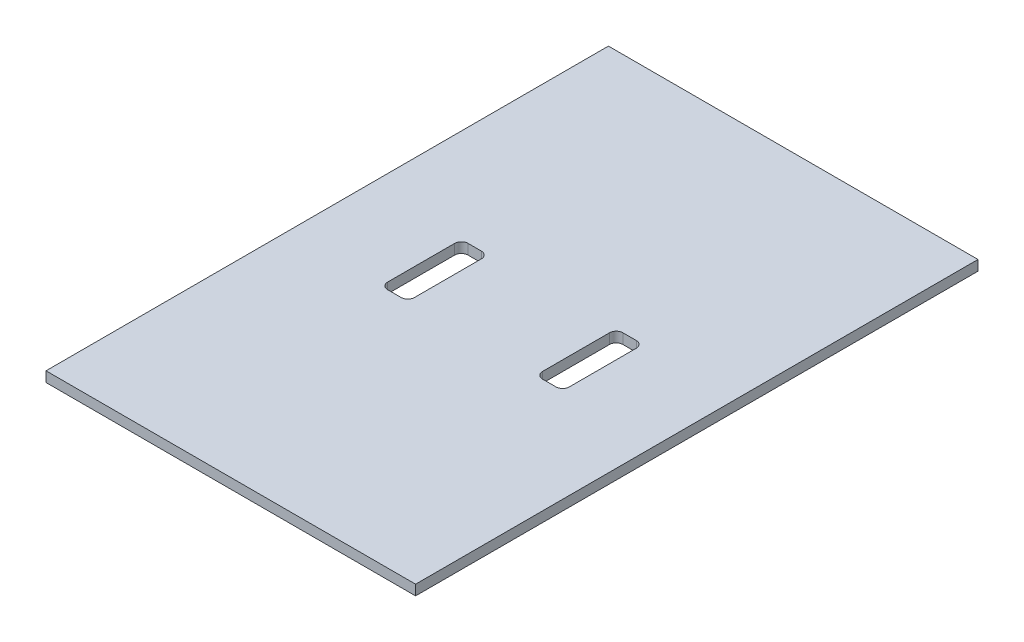
SolidWorks part; units mm, degrees
material "6061-T6 (SS)"
ref_plane "Front Plane" through (0, 0, 0) normal (0, 0, 1) x (1, 0, 0)
ref_plane "Top Plane" through (0, 0, 0) normal (0, 1, 0) x (1, 0, 0)
ref_plane "Right Plane" through (0, 0, 0) normal (1, 0, 0) x (0, 0, -1)
sketch "Sketch1" plane through (0, 0, 0) normal (0, 1, 0) x (1, 0, 0)
  line L1 (-87.63, 133.35) -> (87.63, 133.35)
  line L2 (-87.63, 133.35) -> (-87.63, -133.35)
  line L3 (-87.63, -133.35) -> (87.63, -133.35)
  line L4 (87.63, 133.35) -> (87.63, -133.35)
  line L5 (-87.63, 133.35) -> (87.63, -133.35) construction
  line L6 (-87.63, -133.35) -> (87.63, 133.35) construction
  point P0 (0, 0)
  dimension "D1" = 175.26
  dimension "D2" = 266.7
extrude "Boss-Extrude1" add sketch "Sketch1" along normal blind 4.826
sketch "Sketch2" plane through (0, 4.826, 0) normal (0, 1, 0) x (1, 0, 0)
  line L0 (-87.63, 133.35) -> (-87.63, -133.35) construction
  line L1 (-43.0665, 19.05) -> (-30.3665, 19.05)
  line L2 (-43.0665, 19.05) -> (-43.0665, -19.05)
  line L3 (-43.0665, -19.05) -> (-30.3665, -19.05)
  line L4 (-30.3665, 19.05) -> (-30.3665, -19.05)
  line L5 (-43.0665, 19.05) -> (-30.3665, -19.05) construction
  line L6 (-43.0665, -19.05) -> (-30.3665, 19.05) construction
  point P0 (-36.7165, 0)
  point P7 (0, 0)
  point P8 (0, 0)
  dimension "D1" = 50.9135
  dimension "D2" = 12.7
  dimension "D3" = 38.1
extrude "Cut-Extrude1" cut sketch "Sketch2" against normal through all
mirror "Mirror1" about plane through (0, 0, 0) normal (1, 0, 0) of "Cut-Extrude1"
fillet "Fillet1" radius 3.175 8 edges at (43.0665, 2.413, 19.05) (30.3665, 2.413, 19.05) (43.0665, 2.413, -19.05) (30.3665, 2.413, -19.05) (-30.3665, 2.413, 19.05) (-43.0665, 2.413, 19.05) (-30.3665, 2.413, -19.05) (-43.0665, 2.413, -19.05)
